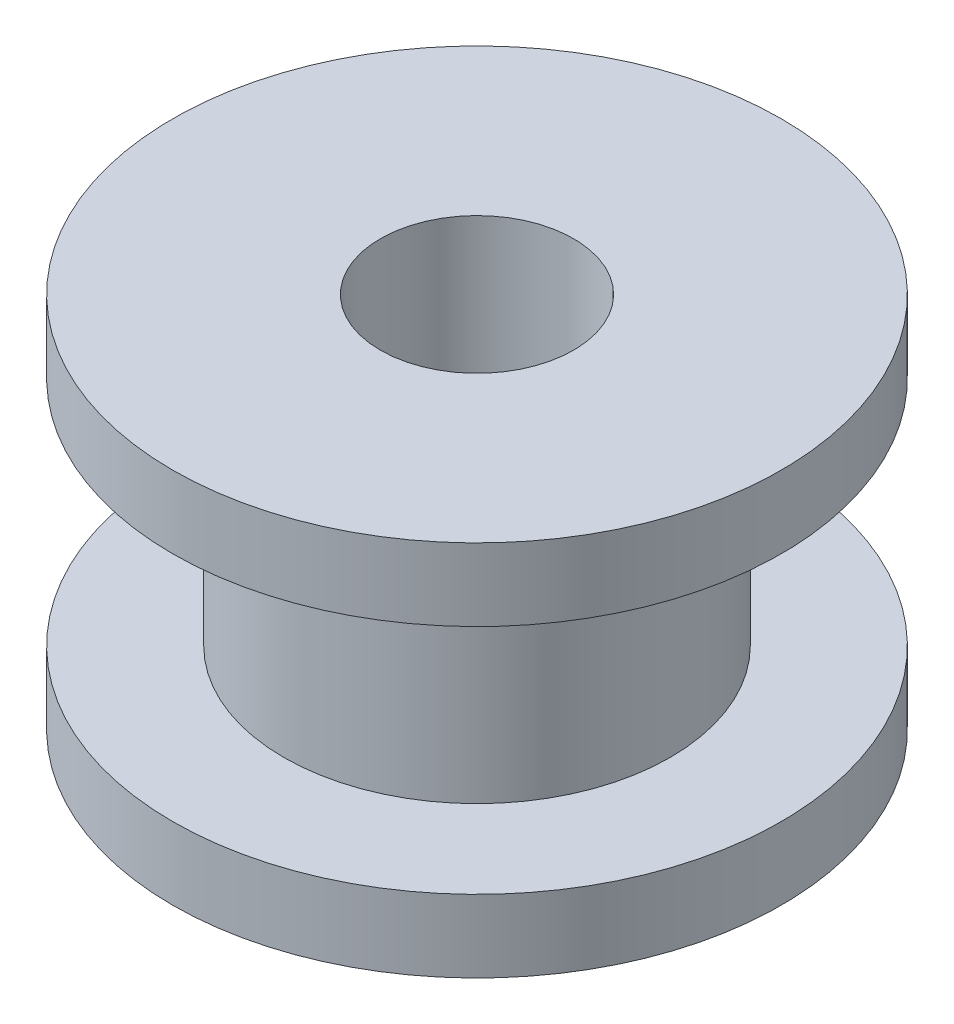
SolidWorks part; units mm, degrees
ref_plane "Front" through (0, 0, 0) normal (0, 0, 1) x (1, 0, 0)
ref_plane "Top" through (0, 0, 0) normal (0, 1, 0) x (1, 0, 0)
ref_plane "Right" through (0, 0, 0) normal (1, 0, 0) x (0, 0, -1)
sketch "Sketch1" plane through (0, 0, 0) normal (0, 1, 0) x (1, 0, 0)
  circle A0 centre (0, 0) radius 8
  circle A1 centre (0, 0) radius 2.54
  dimension "D1" = 16
  dimension "D2" = 5.08
extrude "Boss-Extrude1" add sketch "Sketch1" along normal blind 9.906
ref_plane "Plane1" through (0, 1.905, 0) normal (0, 1, 0) x (1, 0, 0)
sketch "Sketch2" plane through (0, 1.905, 0) normal (0, 1, 0) x (1, 0, 0)
  circle A0 centre (0, 0) radius 5.08
  circle A1 centre (0, 0) radius 8
  circle A2 centre (0, 0) radius 8
  circle A3 centre (0, 0) radius 2.54 construction
  dimension "D2" = 2.54
  dimension "D1" = 0
extrude "Cut-Extrude1" cut sketch "Sketch2" along normal blind 6.096
